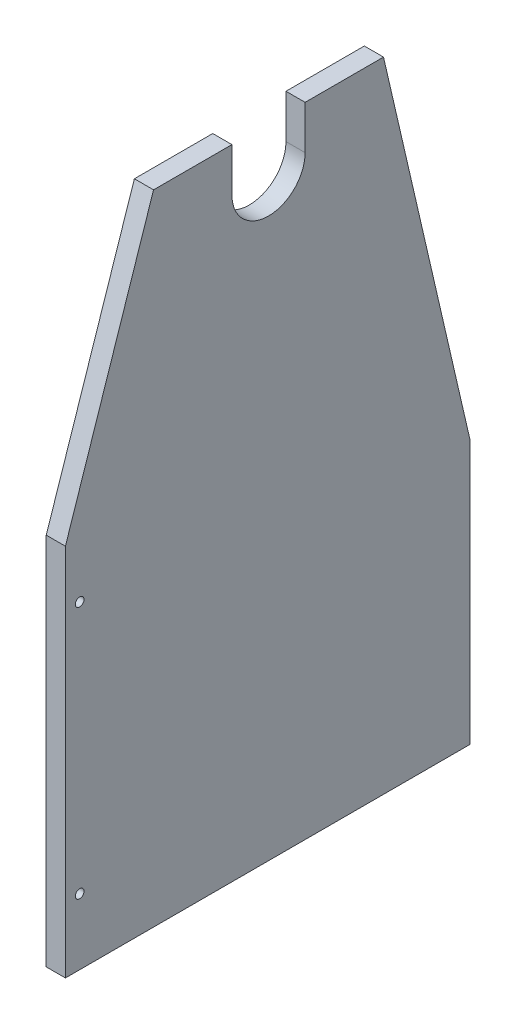
SolidWorks part; units mm, degrees
ref_plane "Front Plane" through (0, 0, 0) normal (0, 0, 1) x (1, 0, 0)
ref_plane "Top Plane" through (0, 0, 0) normal (0, 1, 0) x (1, 0, 0)
ref_plane "Right Plane" through (0, 0, 0) normal (1, 0, 0) x (0, 0, -1)
sketch "Sketch1" plane through (0, 0, 0) normal (1, 0, 0) x (0, 0, -1)
  line L0 (0, 0) -> (368.3, 0)
  line L1 (368.3, 0) -> (368.3, 241.3)
  line L2 (368.3, 241.3) -> (289.7358, 581.5987)
  line L8 (80.2643, 581.5987) -> (0, 340.614)
  line L9 (0, 340.614) -> (0, 0)
  line L10 (80.2643, 581.5987) -> (289.7358, 581.5987)
  dimension "D1" = 368.3
  dimension "D2" = 340.614
  dimension "D3" = 241.3
  dimension "D4" = 349.25
  dimension "D5" = 254
  dimension "D6" = 167
extrude "Boss-Extrude1" add sketch "Sketch1" along normal blind 17.4625
sketch "RockerBoxCutout" plane through (17.4625, 0, 0) normal (1, 0, 0) x (0, 0, -1)
  line L0 (151.6626, 541.9112) -> (151.6626, 581.5987)
  line L1 (151.6626, 541.9112) -> (218.3376, 541.9112)
  line L2 (151.6626, 581.5987) -> (218.3376, 581.5987)
  line L3 (218.3376, 541.9112) -> (218.3376, 581.5987)
  line L4 (151.6626, 541.9112) -> (218.3376, 581.5987) construction
  line L5 (151.6626, 581.5987) -> (218.3376, 541.9112) construction
  line L6 (289.7358, 581.5987) -> (80.2643, 581.5987) construction
  circle A0 centre (185.0001, 541.9112) radius 33.3375
  point P1 (185.0001, 561.755)
  point P3 (185.0001, 581.5987)
  line M9 (289.7358, 581.5987) -> (80.2643, 581.5987)
  dimension "D1" = 66.675
  dimension "D2" = 39.6875
extrude "Cut-Extrude1" cut sketch "RockerBoxCutout" against normal up to surface (17.4625 mm away) contours L1 A0 | L1 A0 | A0 L3 L0 M9 region at (17.4625, 556.0601, -185.0001) region at (17.4625, 561.755, -152.4385) region at (17.4625, 527.7624, -185.0001) up to face at (0, 290.8519, -184.4334)
sketch "Sketch2" plane through (0, 0, 0) normal (-1, 0, 0) x (0, 0, 1)
  line L0 (0, 0) -> (-368.3, 0) construction
  circle A0 centre (-13, 60) radius 3.9688
  circle A1 centre (-13, 290.1875) radius 3.9688
  dimension "D1" = 7.9375
  dimension "D2" = 7.9375
  dimension "D3" = 60
  dimension "D4" = 13
  dimension "D5" = 13
  dimension "D6" = 230.1875
extrude "Cut-Extrude2" cut sketch "Sketch2" against normal up to surface (17.4625 mm away) up to face at (17.4625, 395.8794, -184.66)
